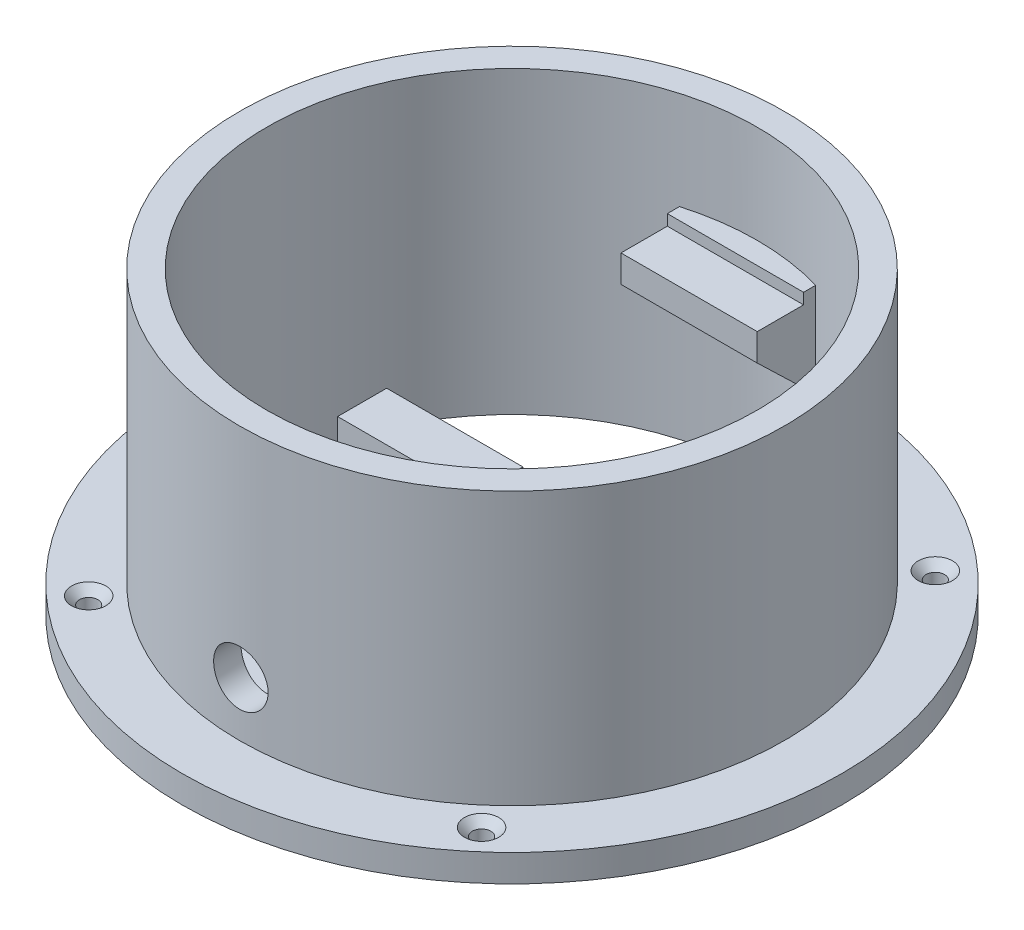
SolidWorks part; units mm, degrees
material "ABS"
ref_plane "Front Plane" through (0, 0, 0) normal (0, 0, 1) x (1, 0, 0)
ref_plane "Top Plane" through (0, 0, 0) normal (0, 1, 0) x (1, 0, 0)
ref_plane "Right Plane" through (0, 0, 0) normal (1, 0, 0) x (0, 0, -1)
sketch "Sketch1" plane through (0, 0, 0) normal (0, 1, 0) x (1, 0, 0)
  line L0 (-14, -10.5) -> (14, -10.5)
  line L1 (-14, -10.5) -> (-35.0784, -28.1869)
  line L2 (0, 69.9597) -> (0, -81.7794) construction
  line L3 (14, -10.5) -> (35.0784, -28.1869)
  line L7 (-17.5, -23.5) -> (-23.6284, -28.6423)
  line L8 (17.5, -23.5) -> (23.6284, -28.6423)
  line L10 (-17.5, -23.5) -> (17.5, -23.5)
  circle A0 centre (0, 0) radius 60.5
  arc A1 (35.0784, -28.1869) -> (-35.0784, -28.1869) centre (0, 0) ccw
  arc A2 (-23.6284, -28.6423) -> (23.6284, -28.6423) centre (0, 2.9545) ccw
  point P7 (0, -10.5)
  point P8 (0, -60.5)
  point P15 (0, -36.5)
  point P23 (0, -23.5)
  dimension "D1" = 121
  dimension "D2" = 90
  dimension "D10" = 13
  dimension "D3" = 50
  dimension "D4" = 140
  dimension "D5" = 28
  dimension "D7" = 35
  dimension "D6" = 8
  dimension "D8" = 13
extrude "Boss-Extrude1" add sketch "Sketch1" along normal blind 5
sketch "Sketch2" plane through (0, 5, 0) normal (0, 1, 0) x (1, 0, 0)
  circle A0 centre (0, 0) radius 50
  arc A1 (35.0784, -28.1869) -> (-35.0784, -28.1869) centre (0, 0) ccw construction
  circle A2 centre (0, 0) radius 45
extrude "Boss-Extrude2" add sketch "Sketch2" along normal blind 50
sketch "Sketch3" plane through (0, 5, 0) normal (0, 1, 0) x (1, 0, 0)
  line L0 (-14, -10.5) -> (14, -10.5) construction
  line L1 (-12.5, -10.5) -> (12.5, -10.5)
  line L2 (-12.5, -10.5) -> (-12.5, -19.5)
  line L3 (-12.5, -19.5) -> (12.5, -19.5)
  line L4 (12.5, -10.5) -> (12.5, -19.5)
  line L5 (-12.5, -10.5) -> (12.5, -19.5) construction
  line L6 (-12.5, -19.5) -> (12.5, -10.5) construction
  line L12 (-12.5, -10.5) -> (-4.5, -10.5)
  line L13 (-12.5, -10.5) -> (-12.5, -19.5)
  line L14 (-12.5, -19.5) -> (-4.5, -19.5)
  line L15 (-4.5, -10.5) -> (-4.5, -19.5)
  line L16 (-12.5, -10.5) -> (-4.5, -19.5) construction
  line L17 (-12.5, -19.5) -> (-4.5, -10.5) construction
  line L18 (12.5, -10.5) -> (4.5, -10.5)
  line L19 (12.5, -10.5) -> (12.5, -19.5)
  line L20 (12.5, -19.5) -> (4.5, -19.5)
  line L21 (4.5, -10.5) -> (4.5, -19.5)
  line L22 (12.5, -10.5) -> (4.5, -19.5) construction
  line L23 (12.5, -19.5) -> (4.5, -10.5) construction
  point P4 (0, -15)
  point P7 (0, -10.5)
  point P8 (0, -10.5)
  point P11 (-8.5, -15)
  point P14 (8.5, -15)
  point P15 (-12.5, -15)
  line M12 (14, -10.5) -> (-14, -10.5)
  dimension "D1" = 25
  dimension "D2" = 8
  dimension "D3" = 8
  dimension "D4" = 9
extrude "Boss-Extrude3" add sketch "Sketch3" along normal blind 1 contours L21 L1 L15 L3 region at (0, 5, 15)
extrude "Boss-Extrude4" add sketch "Sketch3<3>" along normal blind 25 contours L15 L1 L2 L3 | L21 L3 L4 M12 region at (-8.5, 5, 15) region at (8.5, 5, 15)
sketch "Sketch3<3>" plane through (0, 5, 0) normal (0, 1, 0) x (1, 0, 0) same geometry as "Sketch3"
sketch "Sketch4" plane through (0, 30, 0) normal (0, 1, 0) x (1, 0, 0)
  line L1 (-12.5, -10.5) -> (12.5, -10.5)
  line L2 (-12.5, -10.5) -> (-12.5, -19.5)
  line L3 (-12.5, -19.5) -> (12.5, -19.5)
  line L4 (12.5, -10.5) -> (12.5, -19.5)
  line L5 (-12.5, -10.5) -> (12.5, -19.5) construction
  line L6 (-12.5, -19.5) -> (12.5, -10.5) construction
  point P4 (0, -15)
extrude "Boss-Extrude5" add sketch "Sketch4" along normal blind 5
sketch "Sketch5" plane through (0, 0, 0) normal (1, 0, 0) x (0, 0, -1)
  line L0 (41, 35) -> (32.5, 35)
  line L1 (32.5, 35) -> (32.5, 30)
  line L2 (32.5, 30) -> (46, 17)
  line L3 (46, 17) -> (46, 37)
  line L4 (41, 35) -> (41, 37)
  line L5 (41, 37) -> (46, 37)
  line L7 (50, 55) -> (-50, 55) construction
  line L9 (50, 5) -> (50, 55) construction
  line L10 (-10.5, 30) -> (-10.5, 6) construction
  dimension "D1" = 43
  dimension "D2" = 4
  dimension "D3" = 5
  dimension "D4" = 2
  dimension "D5" = 5
  dimension "D6" = 20
  dimension "D7" = 20
  dimension "D8" = 8.5
extrude "Boss-Extrude7" add sketch "Sketch5" along normal mid plane 25
sketch "Sketch7" plane through (0, 5, 0) normal (0, 1, 0) x (1, 0, 0)
  circle A0 centre (36, -41.5812) radius 3 construction
  circle A1 centre (0, 0) radius 55 construction
  point P5 (-36.842, -40.8371)
  point P6 (36.842, 40.8371)
  point P7 (-36.842, 40.8371)
  point P9 (36, -41.5812)
  dimension "D1" = 110
  dimension "D3" = 6
  dimension "D2" = 36
hole_wizard "CSK for M3 Flat Head Machine Screw1" positions "Sketch8" profile "Sketch9" countersink size "M3" standard "ANSI Metric" end condition up to next
sketch "Sketch8" plane through (0, 5, 0) normal (0, 1, 0) x (1, 0, 0)
  point P0 (-36.842, 40.8371)
  point P3 (36.842, 40.8371)
  point P6 (36, -41.5812)
  point P9 (-36.842, -40.8371)
sketch "Sketch9" plane through (-36.842, 5, -40.8371) normal (1, 0, 0) x (0, 0, 1)
  line L0 (0, 0) -> (0, 5)
  line L1 (0, 5) -> (1.7, 5)
  line L2 (1.7, 5) -> (1.7, 1.45)
  line L3 (1.7, 1.45) -> (3.15, 0)
  line L5 (3.15, 0) -> (0, 0)
  line L6 (-1.7, 1.45) -> (-3.15, 0) construction
  line L11 (0, -6.35) -> (0, 107.95) construction
  dimension "Thru Hole Dia." = 3.4
  dimension "Thru Hole Depth" = 5
  dimension "Near C'Sink Dia." = 6.3
  dimension "Near C'Sink Angle" = 90
ref_plane "Plane1" through (0, 0, 69.5) normal (0, 0, 1) x (1, 0, 0)
sketch "Sketch10" plane through (0, 0, 69.5) normal (0, 0, 1) x (1, 0, 0)
  circle A0 centre (0, 15) radius 5
  dimension "D1" = 10
  dimension "D2" = 15
extrude "Cut-Extrude1" cut sketch "Sketch10" against normal up to surface (24.7786 mm away) contours A0 up to face at (0, 27.9078, -44.1145)
